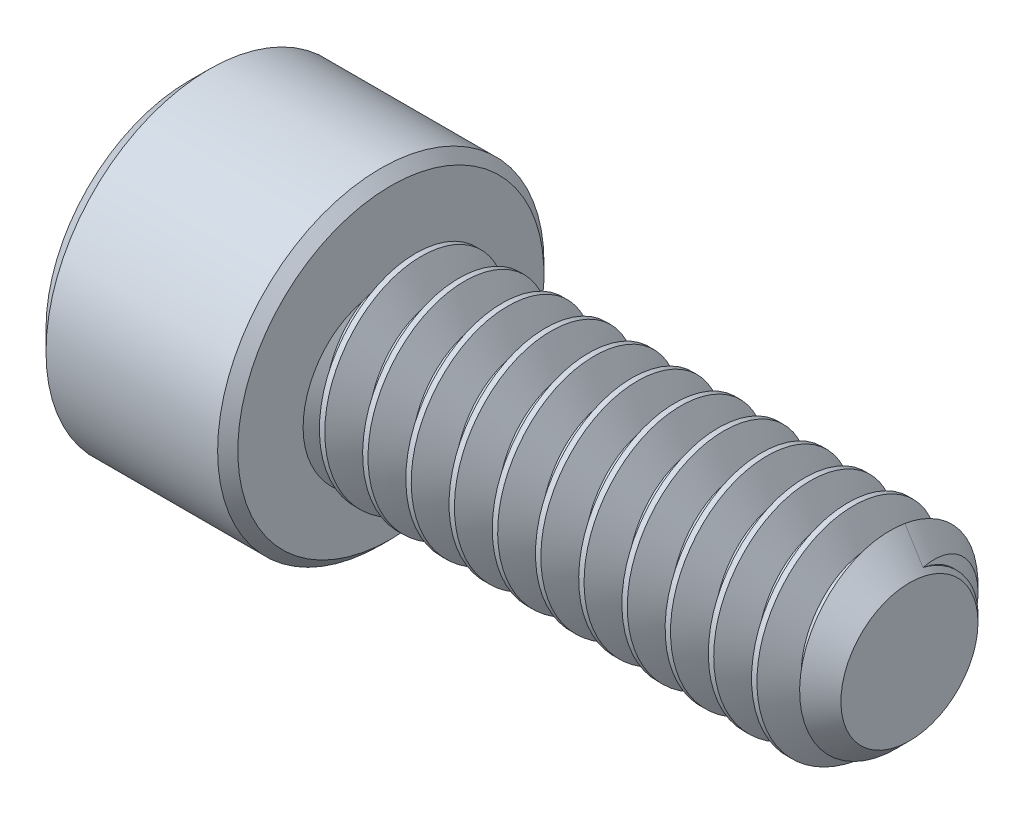
SolidWorks part; units mm, degrees
ref_plane "Front Plane" through (0, 0, 0) normal (0, 0, 1) x (1, 0, 0)
ref_plane "Top Plane" through (0, 0, 0) normal (0, 1, 0) x (1, 0, 0)
ref_plane "Right Plane" through (0, 0, 0) normal (1, 0, 0) x (0, 0, -1)
sketch "Sketch1" plane through (0, 0, 0) normal (0, 0, 1) x (1, 0, 0)
  line L0 (2.3812, 0) -> (-2.3812, 0) construction
  line L1 (2.3812, 0.9271) -> (2.3812, -0.9271) construction
  line L2 (-2.3812, 1.4059) -> (-2.3812, -1.4059) construction
  line L3 (-2.474, 1.4986) -> (-4.05, 1.4986) construction
  line L4 (-4.05, 1.4986) -> (-4.2355, 1.3132) construction
  line L5 (-4.2355, 1.3132) -> (-4.2355, -1.3132) construction
  line L6 (-4.2355, -1.3132) -> (-4.05, -1.4986) construction
  line L7 (-4.05, -1.4986) -> (-2.474, -1.4986) construction
  line L8 (-2.474, 1.4986) -> (-2.3812, 1.4059) construction
  line L9 (-2.3812, -1.4059) -> (-2.474, -1.4986) construction
  point P5 (-2.3812, 1.4986)
  point P6 (-2.3812, -1.4986)
  point P7 (-3.4481, 0)
  point P12 (0.7937, -0.9271)
  dimension "D1" = 45
  dimension "Dec." = 1.8542
  dimension "Length" = 4.7625
  dimension "Head Dia" = 2.9972
  dimension "Head Height" = 1.8542
  dimension "Hex Depth" = 0.7874
  dimension "Chamfer" = 0.1854
  dimension "D2" = 1.5875
  dimension "D3" = 0.0927
  dimension "D4" = 45
ref_plane "Plane1" through (2.3812, 0, 0) normal (1, 0, 0) x (0, 0, -1)
ref_plane "Plane2" through (-4.2355, 0, 0) normal (1, 0, 0) x (0, 0, -1)
sketch "Sketch2" plane through (2.3812, 0, 0) normal (1, 0, 0) x (0, 0, -1)
  circle A0 centre (0, 0) radius 0.9271
extrude "Boss-Extrude1" add sketch "Sketch2" against normal up to vertex (4.7625 mm away) up to point (-2.3812, 0, 0)
sketch "Sketch3" plane through (2.3812, 0, 0) normal (1, 0, 0) x (0, 0, -1)
  circle A0 centre (0, 0) radius 0.9271 construction
  circle A1 centre (0, 0) radius 0.9271
curve "Helix/Spiral1" pitch 0.3969 height 5.1594 radius 0.9271 centre (2.3812, 0, 0) axis (-1, 0, 0) start towards (0, 1, 0) parameters "Pitch"=0.3969
chamfer "Chamfer1" distance 0.2977 angle 45 1 edges at (2.3812, 0, -0.9271)
sketch "Sketch5" plane through (0, 0, 0) normal (0, 0, 1) x (1, 0, 0)
  line L0 (2.2076, 0.9271) -> (2.5549, 0.9271)
  line L1 (2.5549, 0.9271) -> (2.4061, 0.6693)
  line L2 (2.4061, 0.6693) -> (2.3564, 0.6693)
  line L3 (2.3564, 0.6693) -> (2.2076, 0.9271)
  line L4 (2.3812, 0.6693) -> (2.3812, 0.9271) construction
  line L5 (2.282, 0.7982) -> (2.4805, 0.7982) construction
  dimension "D1" = 60
  dimension "D2" = 0.1984
  dimension "D3" = 0.0496
sweep "Cut-Sweep1" cut profiles "Sketch5" path "Helix/Spiral1" align with end faces yes
sketch "Sketch4" plane through (-4.2355, 0, 0) normal (1, 0, 0) x (0, 0, -1)
  line L0 (-1.4986, 0.7937) -> (1.4986, 0.7937) construction
  line L1 (0, 0.9165) -> (-0.7937, 0.4583)
  line L2 (-0.7937, 0.4583) -> (-0.7937, -0.4583)
  line L3 (-0.7937, -0.4583) -> (0, -0.9165)
  line L4 (0, -0.9165) -> (0.7937, -0.4583)
  line L5 (0.7937, -0.4583) -> (0.7937, 0.4583)
  line L6 (0.7937, 0.4583) -> (0, 0.9165)
  line L7 (0, 0) -> (0, 0.7937) construction
  circle A0 centre (0, 0) radius 0.7937 construction
  dimension "Hex Size" = 1.5875
  dimension "D1" = 2.9972
  dimension "D2" = 0.7937
sketch "Sketch6" plane through (0, 0, 0) normal (0, 0, 1) x (1, 0, 0)
  line L0 (-4.05, 1.4986) -> (-4.2355, 1.3132) construction
  line L2 (-2.3812, 1.4059) -> (-2.3812, -1.4059) construction
  line L3 (-4.2355, 1.3132) -> (-4.2355, -1.3132) construction
  line L4 (-4.05, 1.4986) -> (-4.2355, 1.3132)
  line L5 (-2.474, 1.4986) -> (-4.05, 1.4986) construction
  line L6 (-2.3812, 1.4059) -> (-2.3812, 0)
  line L7 (-4.2355, 1.3132) -> (-4.2355, 0)
  line L8 (-2.3812, 0) -> (-4.2355, 0) construction
  line L9 (-2.3812, 0) -> (-4.2355, 0)
  line L10 (-2.474, 1.4986) -> (-2.3812, 1.4059) construction
  line L11 (-2.474, 1.4986) -> (-4.05, 1.4986)
  line L12 (-2.474, 1.4986) -> (-2.3812, 1.4059)
revolve "Revolve1" add sketch "Sketch6" angle 360 about L8
extrude "Cut-Extrude1" cut sketch "Sketch4" along normal up to vertex (0.7874 mm away) up to point (-3.4481, 0, 0)
sketch "Sketch8" plane through (-4.2355, 0, 0) normal (-1, 0, 0) x (0, 0, 1)
  circle A1 centre (0, 0) radius 0.9165
extrude "Cut-Extrude2" cut sketch "Sketch8" against normal blind 0.3708 draft 45
equation "\"D3@Helix/Spiral1\" = \"Length@Sketch1\"+\"Pitch@Helix/Spiral1\""
equation "\"D3@Sketch5\" = \"Pitch@Helix/Spiral1\"*.125"
equation "\"D2@Sketch5\" = \"Pitch@Helix/Spiral1\"*.50"
equation "\"D1@Chamfer1\" = \"Pitch@Helix/Spiral1\"*.75"
equation "\"D2@Sketch1\" = \"Pitch@Helix/Spiral1\"*4"
equation "\"D1@Sketch4\" = \"Head Dia@Sketch1\""
equation "\"Chamfer@Sketch1\" = \"Head Height@Sketch1\"/10"
equation "\"D3@Sketch1\" = \"Chamfer@Sketch1\"/2"
equation "\"D1@Cut-Extrude2\" = \"Chamfer@Sketch1\"*2"
